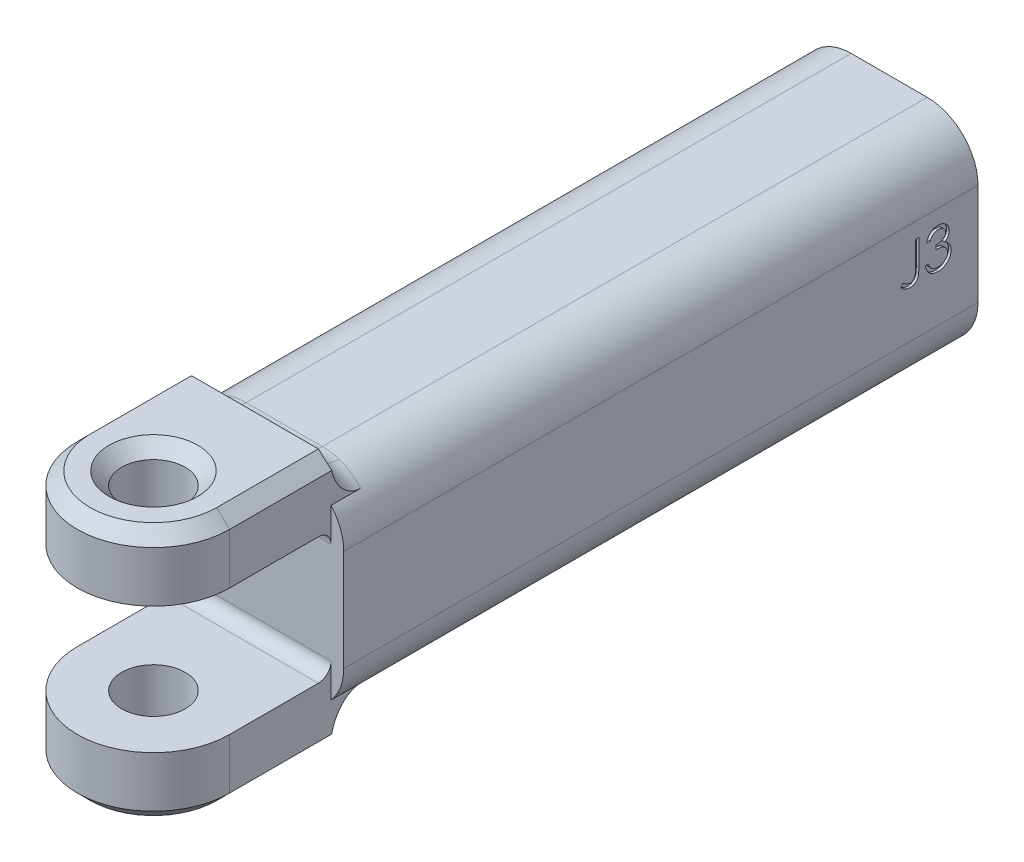
SolidWorks part; units mm, degrees
ref_plane "Alzado" through (0, 0, 0) normal (0, 0, 1) x (1, 0, 0)
ref_plane "Planta" through (0, 0, 0) normal (0, 1, 0) x (1, 0, 0)
ref_plane "Vista lateral" through (0, 0, 0) normal (1, 0, 0) x (0, 0, -1)
sketch "Sketch1" plane through (0, 0, 0) normal (0, 0, 1) x (1, 0, 0)
  line L0 (0, -25) -> (0, 25)
  line L1 (0, 0) -> (10.8734, 0)
  line L2 (42.2279, -50) -> (42.2279, -25)
  line L3 (42.2279, 50) -> (-17.7721, 50)
  line L4 (42.2279, 50) -> (42.2279, 25)
  line L5 (42.2279, 25) -> (-17.7721, 25)
  line L6 (-17.7721, 50) -> (-17.7721, 25)
  line L7 (42.2279, 50) -> (-17.7721, 25) construction
  line L8 (42.2279, 25) -> (-17.7721, 50) construction
  line L9 (42.2279, -25) -> (-17.7721, -25)
  line L10 (-17.7721, -50) -> (-17.7721, -25)
  line L11 (42.2279, -50) -> (-17.7721, -50)
  point P5 (12.2279, 37.5)
  dimension "D1" = 25
  dimension "D2" = 60
  dimension "D3" = 50
extrude "Boss-Extrude1" add sketch "Sketch1" along normal blind 80 contours L11 L2 L9 L10 | L3 L6 L5 L4
fillet "Fillet1" radius 10 2 edges at (42.2279, 37.5, 80) (-17.7721, 37.5, 80)
fillet "Fillet2" radius 10 2 edges at (42.2279, -37.5, 80) (-17.7721, -37.5, 80)
sketch "Sketch2" plane through (0, 0, 0) normal (0, 0, -1) x (-1, 0, 0)
  line L0 (-12.2279, 25) -> (-12.2279, -25)
  line L1 (-42.2279, 25) -> (17.7721, 25) construction
  line L2 (-42.2279, -25) -> (17.7721, -25) construction
  line L4 (-47.2279, -40) -> (22.7721, -40)
  line L5 (-47.2279, -40) -> (-47.2279, 40)
  line L6 (-47.2279, 40) -> (22.7721, 40)
  line L7 (22.7721, -40) -> (22.7721, 40)
  line L8 (-47.2279, -40) -> (22.7721, 40) construction
  line L9 (-47.2279, 40) -> (22.7721, -40) construction
  point P6 (-12.2279, 0)
  dimension "D1" = 70
  dimension "D2" = 80
extrude "Boss-Extrude2" add sketch "Sketch2" along normal blind 250
fillet "Fillet3" radius 20 4 edges at (-22.7721, -40, -125) (47.2279, -40, -125) (47.2279, 40, -125) (-22.7721, 40, -125)
sketch "Sketch3" plane through (0, 50, 0) normal (0, 1, 0) x (1, 0, 0)
  circle A0 centre (12.2279, -40) radius 12.5
  dimension "D1" = 25
extrude "Cut-Extrude1" cut sketch "Sketch3" against normal blind 120
sketch "Sketch4" plane through (0, -50, 0) normal (0, -1, 0) x (1, 0, 0)
  line L0 (-17.7721, 40) -> (-17.7721, 89.1002)
  line L1 (-17.7721, 89.1002) -> (42.2279, 89.1002)
  line L2 (42.2279, 89.1002) -> (42.2279, 40)
  arc A0 (42.2279, 40) -> (-17.7721, 40) centre (12.2279, 40) ccw
extrude "Cut-Extrude2" cut sketch "Sketch4" against normal blind 120
fillet "Fillet6" radius 11.6843 6 edges at (35.4566, 38.2288, 0) (-11.0009, 38.2288, 0) (35.4566, -38.2288, 0) (-11.0009, -38.2288, 0) (12.2279, 40, 0) (12.2279, -40, 0)
fillet "Fillet7" radius 5 2 edges at (12.2279, 25, 0) (12.2279, -25, 0)
chamfer "Chamfer2" distance 5 angle 45 6 edges at (-17.7721, 50, 20) (12.2279, 50, 70) (42.2279, 50, 20) (-17.7721, -50, 20) (12.2279, -50, 70) (42.2279, -50, 20)
sketch "Sketch5" plane through (0, 0, -250) normal (0, 0, -1) x (-1, 0, 0)
  line L1 (-42.0376, -30) -> (17.9624, -30)
  line L2 (-42.0376, -30) -> (-42.0376, 30)
  line L3 (-42.0376, 30) -> (17.9624, 30)
  line L4 (17.9624, -30) -> (17.9624, 30)
  point P0 (-12.0376, 0)
  dimension "D1" = 60
  dimension "D2" = 60
extrude "Cut-Extrude3" cut sketch "Sketch5" against normal blind 150
fillet "Fillet8" radius 10 4 edges at (-17.9624, 30, -175) (-17.9624, -30, -175) (42.0376, -30, -175) (42.0376, 30, -175)
sketch "Sketch6" plane through (47.2279, 0, 0) normal (1, 0, 0) x (0, 0, -1)
  text T0 "J3" font "Century Gothic" height 15
extrude "Cut-Extrude4" cut sketch "Sketch6" against normal blind 1
chamfer "Chamfer3" distance 5 angle 45 2 edges at (24.7279, -50, 40) (12.2279, 50, 52.5)
